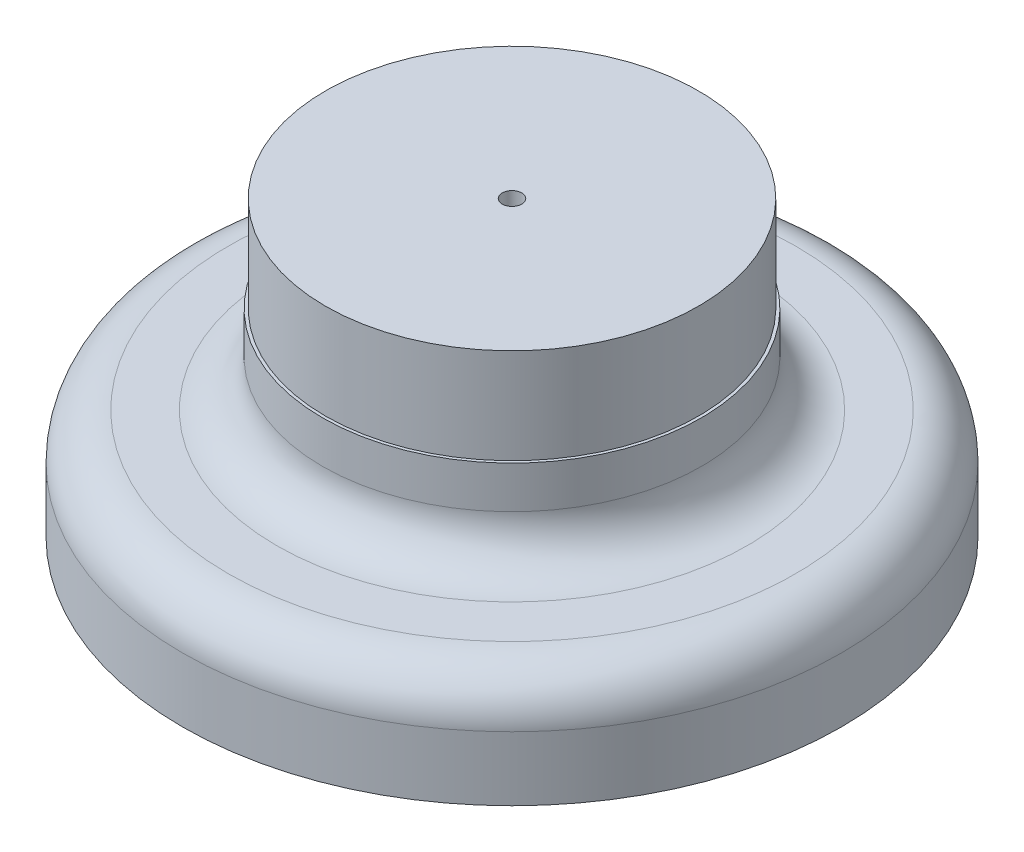
SolidWorks part; units mm, degrees
ref_plane "Front Plane" through (0, 0, 0) normal (0, 0, 1) x (1, 0, 0)
ref_plane "Top Plane" through (0, 0, 0) normal (0, 1, 0) x (1, 0, 0)
ref_plane "Right Plane" through (0, 0, 0) normal (1, 0, 0) x (0, 0, -1)
sketch "Sketch1" plane through (0, 0, 0) normal (0, 1, 0) x (1, 0, 0)
  circle A0 centre (0, 0) radius 64.7065
  circle A1 centre (0, 0) radius 65.7225
  circle A2 centre (0, 0) radius 114.3
extrude "Boss-Extrude1" add sketch "Sketch1" along normal blind 38.1 contours A2 A1 region at (-111.0671, 0, 0)
extrude "Boss-Extrude2" add sketch "Sketch1<3>" along normal blind 68.58 contours A1 A0 region at (-65.5366, 0, 0)
sketch "Sketch1<3>" plane through (0, 0, 0) normal (0, 1, 0) x (1, 0, 0) same geometry as "Sketch1"
extrude "Boss-Extrude3" add sketch "Sketch1<4>" along normal blind 101.6 contours A0 region at (0, 0, 0)
sketch "Sketch1<4>" plane through (0, 0, 0) normal (0, 1, 0) x (1, 0, 0) same geometry as "Sketch1"
hole_wizard "CSK for 1/4 Flat Head Machine Screw (100)1" positions "Sketch2" profile "Sketch3" countersink size "1/4" standard "ANSI Inch" end condition through all
sketch "Sketch2" plane through (0, 0, 0) normal (0, -1, 0) x (-1, 0, 0)
  point P0 (0, 0)
sketch "Sketch3" plane through (0, 0, 0) normal (1, 0, 0) x (0, 0, -1)
  line L0 (0, 0) -> (0, 101.6)
  line L1 (0, 101.6) -> (3.3782, 101.6)
  line L2 (3.3782, 101.6) -> (3.3782, 2.5682)
  line L3 (3.3782, 2.5682) -> (6.4389, 0)
  line L5 (6.4389, 0) -> (0, 0)
  line L6 (-3.3782, 2.5682) -> (-6.4389, 0) construction
  line L11 (0, -6.35) -> (0, 107.95) construction
  dimension "Thru Hole Dia." = 6.7564
  dimension "Thru Hole Depth" = 101.6
  dimension "Near C'Sink Dia." = 12.8778
  dimension "Near C'Sink Angle" = 100
fillet "Fillet1" radius 15.875 1 edges at (0, 38.1, 65.7225)
fillet "Fillet2" radius 15.875 1 edges at (0, 38.1, 114.3)
